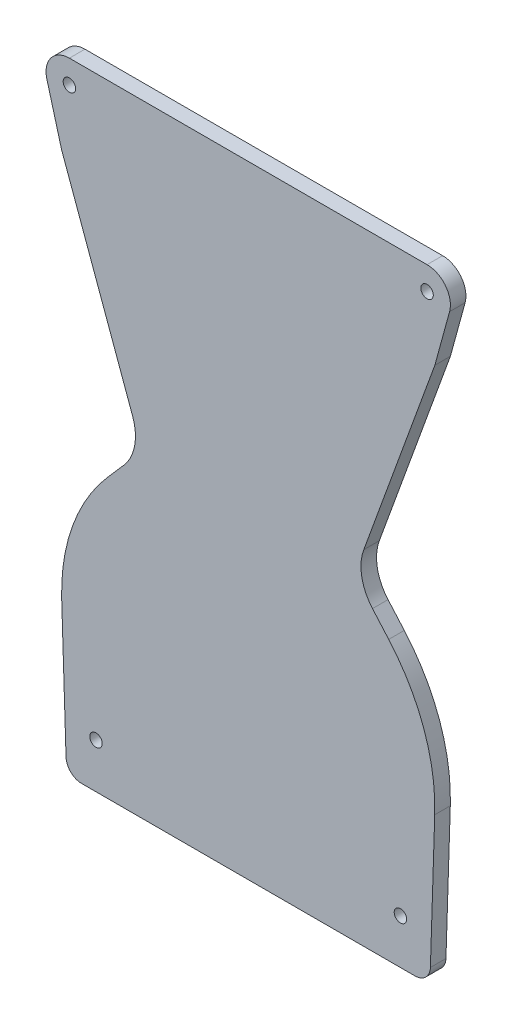
SolidWorks part; units mm, degrees
ref_plane "Front Plane" through (0, 0, 0) normal (0, 0, 1) x (1, 0, 0)
ref_plane "Top Plane" through (0, 0, 0) normal (0, 1, 0) x (1, 0, 0)
ref_plane "Right Plane" through (0, 0, 0) normal (1, 0, 0) x (0, 0, -1)
sketch "Sketch1" plane through (0, 0, 0) normal (0, 0, 1) x (1, 0, 0)
  line L20 (-39.9541, -4.5407) -> (-45.1727, -10.5104) construction
  line L21 (-59.9688, -51.9355) -> (-58.5736, -95.1613) construction
  line L22 (-50, -100) -> (-53.5762, -100) construction
  line L23 (50, -100) -> (-50, -100) construction
  line L24 (53.5762, -100) -> (50, -100) construction
  line L25 (58.5736, -95.1613) -> (59.9688, -51.9355) construction
  line L26 (39.9541, -4.5407) -> (45.1727, -10.5104) construction
  line L27 (60, 73.2367) -> (37.1519, 10.462) construction
  line L28 (64.7336, 90.5187) -> (60, 73.2367) construction
  line L29 (-57.5, 100) -> (-55, 100) construction
  line L30 (55, 100) -> (57.5, 100) construction
  line L31 (-55, 100) -> (55, 100) construction
  line L32 (-64.7336, 90.5187) -> (-60, 73.2367) construction
  line L33 (-60, 73.2367) -> (-37.1519, 10.462) construction
  line L34 (-39.9541, -4.5407) -> (-45.1727, -10.5104)
  line L35 (-59.9688, -51.9355) -> (-58.5736, -95.1613)
  line L36 (-50, -100) -> (-53.5762, -100)
  line L37 (50, -100) -> (-50, -100)
  line L38 (53.5762, -100) -> (50, -100)
  line L39 (58.5736, -95.1613) -> (59.9688, -51.9355)
  line L40 (39.9541, -4.5407) -> (45.1727, -10.5104)
  line L41 (60, 73.2367) -> (37.1519, 10.462)
  line L42 (64.7336, 90.5187) -> (60, 73.2367)
  line L43 (-57.5, 100) -> (-55, 100)
  line L44 (55, 100) -> (57.5, 100)
  line L45 (-55, 100) -> (55, 100)
  line L46 (-64.7336, 90.5187) -> (-60, 73.2367)
  line L47 (-60, 73.2367) -> (-37.1519, 10.462)
  arc A20 (-39.9541, -4.5407) -> (-37.1519, 10.462) centre (-51.2472, 5.3317) ccw construction
  arc A21 (-45.1727, -10.5104) -> (-59.9688, -51.9355) centre (0, -50) ccw construction
  arc A22 (-58.5736, -95.1613) -> (-53.5762, -100) centre (-53.5762, -95) ccw construction
  arc A23 (53.5762, -100) -> (58.5736, -95.1613) centre (53.5762, -95) ccw construction
  arc A24 (59.9688, -51.9355) -> (45.1727, -10.5104) centre (0, -50) ccw construction
  arc A25 (37.1519, 10.462) -> (39.9541, -4.5407) centre (51.2472, 5.3317) ccw construction
  arc A26 (64.7336, 90.5187) -> (57.5, 100) centre (57.5, 92.5) ccw construction
  arc A27 (-57.5, 100) -> (-64.7336, 90.5187) centre (-57.5, 92.5) ccw construction
  arc A28 (-39.9541, -4.5407) -> (-37.1519, 10.462) centre (-51.2472, 5.3317) ccw
  arc A29 (-45.1727, -10.5104) -> (-59.9688, -51.9355) centre (0, -50) ccw
  arc A30 (-58.5736, -95.1613) -> (-53.5762, -100) centre (-53.5762, -95) ccw
  arc A31 (53.5762, -100) -> (58.5736, -95.1613) centre (53.5762, -95) ccw
  arc A32 (59.9688, -51.9355) -> (45.1727, -10.5104) centre (0, -50) ccw
  arc A33 (37.1519, 10.462) -> (39.9541, -4.5407) centre (51.2472, 5.3317) ccw
  arc A34 (64.7336, 90.5187) -> (57.5, 100) centre (57.5, 92.5) ccw
  arc A35 (-57.5, 100) -> (-64.7336, 90.5187) centre (-57.5, 92.5) ccw
  circle A36 centre (-57.5, 92.5) radius 2
  circle A37 centre (57.5, 92.5) radius 2
  circle A38 centre (48.9391, -85.5982) radius 2
  circle A39 centre (-48.9391, -85.5982) radius 2
  dimension "D1" = 4
extrude "Boss-Extrude1" add sketch "Sketch1" along normal blind 5
sketch "Sketch2" plane through (0, 0, 0) normal (0, 0, -1) x (-1, 0, 0)
  line L0 (-26.5846, 10.6667) -> (-24.7233, 5.5529) construction
  line L1 (-24.7233, 5.5529) -> (-50, 75) construction
  line L2 (-24.3503, 0) -> (24.3503, 0) construction
  line L3 (-22.7022, 0) -> (22.7022, 0) construction
  line L4 (-26.5846, 10.6667) -> (26.5846, 10.6667) construction
  line L5 (26.5846, 10.6667) -> (24.7233, 5.5529) construction
  line L6 (-23.7479, 0.5) -> (23.7479, 0.5)
  line L7 (25.8705, 10.1667) -> (24.2535, 5.7239)
  line L8 (-25.8705, 10.1667) -> (25.8705, 10.1667)
  line L9 (-25.8705, 10.1667) -> (-24.2535, 5.7239)
  arc A0 (-24.7233, 5.5529) -> (-24.3503, 0) centre (-34.1202, 2.1327) cw construction
  arc A2 (24.7233, 5.5529) -> (24.3503, 0) centre (34.1202, 2.1327) ccw construction
  arc A3 (24.2535, 5.7239) -> (23.7479, 0.5) centre (34.1202, 2.1327) ccw
  arc A4 (-24.2535, 5.7239) -> (-23.7479, 0.5) centre (-34.1202, 2.1327) cw
  point P5 (0, 0)
  point P17 (-24.7233, 0)
  point P18 (24.4119, -0.2649)
  dimension "D1" = 0.5
extrude "Boss-Extrude2" add sketch "Sketch2" along normal blind 10
chamfer "Chamfer2" distance 10 distance2 10 1 edges at (0, 10.1667, -10)
